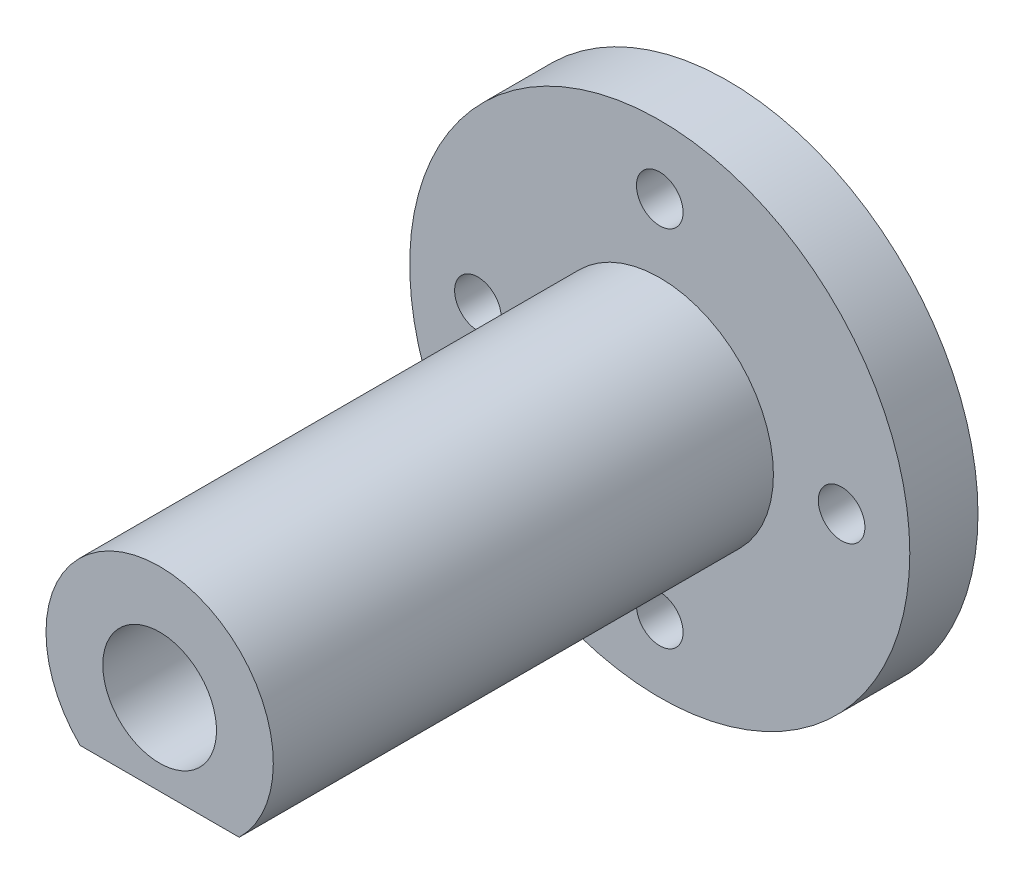
SolidWorks part; units mm, degrees
ref_plane "Front Plane" through (0, 0, 0) normal (1, 0, 0) x (0, 1, 0)
ref_plane "Top Plane" through (0, 0, 0) normal (0, 0, 1) x (0, 1, 0)
ref_plane "Right Plane" through (0, 0, 0) normal (0, 1, 0) x (-1, 0, 0)
sketch "Sketch1" plane through (0, 0, 0) normal (0, 0, 1) x (0, 1, 0)
  line L0 (0, 8) -> (0, 0) construction
  circle A0 centre (0, 0) radius 11
  circle A1 centre (0, 8) radius 1.025
  circle A2 centre (0, 0) radius 4.25
  circle A3 centre (8, 0) radius 1.025
  circle A4 centre (0, -8) radius 1.025
  circle A5 centre (-8, 0) radius 1.025
  point P6 (4.7842, -11.2785)
  point P7 (0, 0)
  point P15 (0, 0)
  dimension "D1" = 22
  dimension "D2" = 8
  dimension "D3" = 2.05
  dimension "D4" = 8.5
  dimension "D5" = 4
extrude "Boss-Extrude1" add sketch "Sketch1" along normal blind 3
sketch "Sketch2" plane through (0, 0, 3) normal (0, 0, 1) x (1, 0, 0)
  circle A1 centre (0, 0) radius 5
  circle A2 centre (0, 0) radius 2.5
  dimension "D1" = 5
  dimension "D2" = 10
extrude "Boss-Extrude2" add sketch "Sketch2" along normal offset from surface (22 mm away) 25 up to face at (11, 0, 0)
sketch "Sketch3" plane through (0, 0, 25) normal (0, 0, 1) x (1, 0, 0)
  line L0 (3.5, -3.5707) -> (-3.5, -3.5707)
  circle A0 centre (0, 0) radius 5 construction
  circle A1 centre (0, 0) radius 5 construction
  arc A2 (-3.5, -3.5707) -> (3.5, -3.5707) centre (0, 0) ccw
  dimension "D1" = 7
extrude "Cut-Extrude1" cut sketch "Sketch3" against normal blind 10
